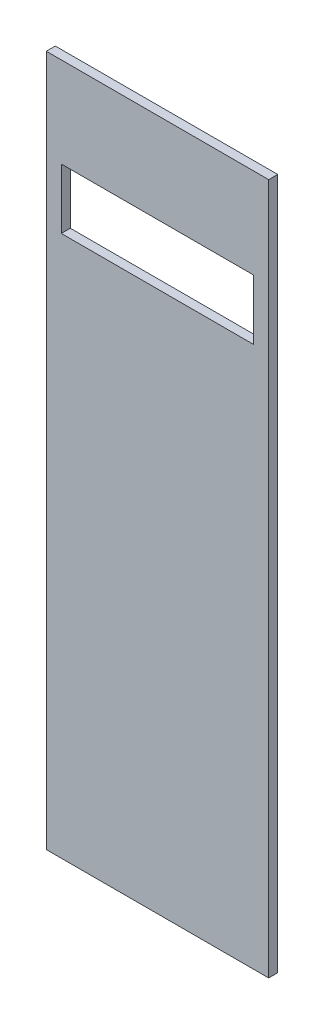
SolidWorks part; units mm, degrees
ref_plane "Plano frontal" through (0, 0, 0) normal (0, 0, 1) x (1, 0, 0)
ref_plane "Plano superior" through (0, 0, 0) normal (0, 1, 0) x (1, 0, 0)
ref_plane "Plano direito" through (0, 0, 0) normal (1, 0, 0) x (0, 0, -1)
sketch "Esboço1" plane through (0, 0, 0) normal (0, 0, 1) x (1, 0, 0)
  line L1 (-185, 575) -> (185, 575)
  line L2 (-185, 575) -> (-185, -575)
  line L3 (-185, -575) -> (185, -575)
  line L4 (185, 575) -> (185, -575)
  line L5 (-185, 575) -> (185, -575) construction
  line L6 (-185, -575) -> (185, 575) construction
  point P0 (0, 0)
  dimension "D1" = 370
  dimension "D2" = 1150
extrude "Ressalto-extrusão1" add sketch "Esboço1" along normal blind 15
sketch "Esboço2" plane through (0, 0, 15) normal (0, 0, 1) x (1, 0, 0)
  line L0 (-185, 575) -> (-185, -575) construction
  line L1 (-160, 425) -> (160, 425)
  line L2 (-160, 425) -> (-160, 325)
  line L3 (-160, 325) -> (160, 325)
  line L4 (160, 425) -> (160, 325)
  line L5 (-160, 425) -> (160, 325) construction
  line L6 (-160, 325) -> (160, 425) construction
  line L7 (185, 575) -> (-185, 575) construction
  point P0 (0, 375)
  dimension "D1" = 320
  dimension "D2" = 185
  dimension "D3" = 100
  dimension "D4" = 150
  dimension "D5" = 25
extrude "Corte-extrusão1" cut sketch "Esboço2" against normal blind 15
